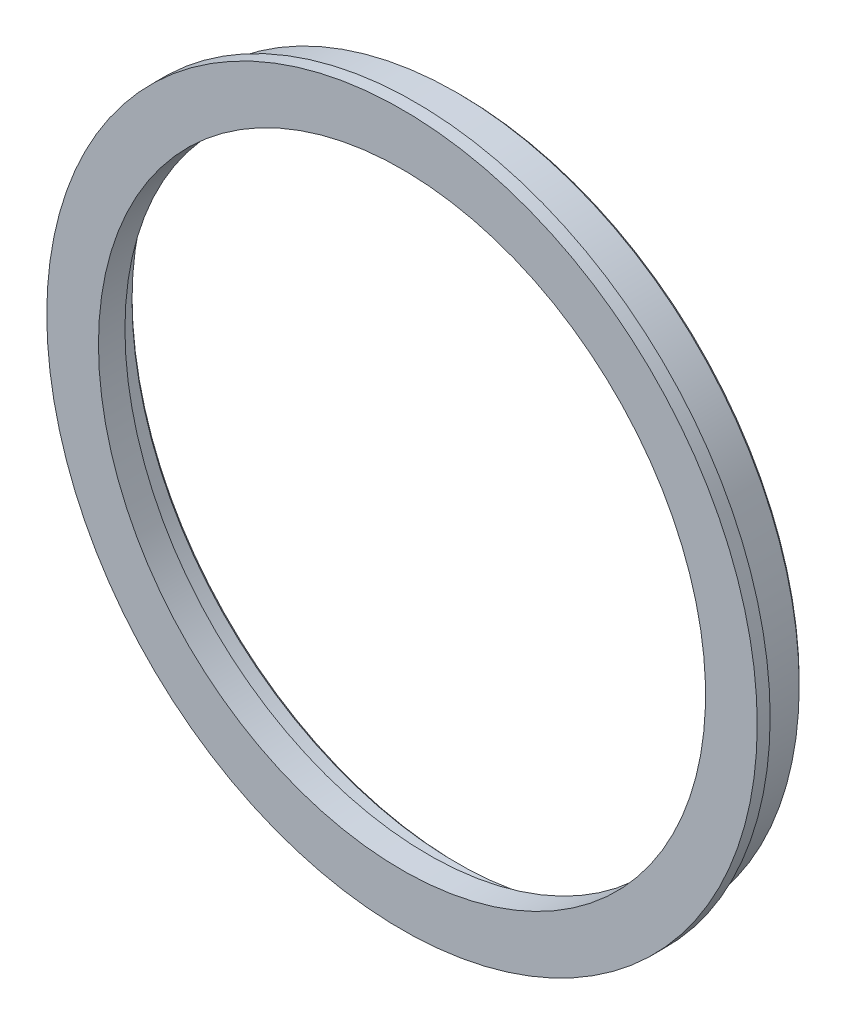
SolidWorks part; units mm, degrees
ref_plane "Front Plane" through (0, 0, 0) normal (0, 0, 1) x (1, 0, 0)
ref_plane "Top Plane" through (0, 0, 0) normal (0, 1, 0) x (1, 0, 0)
ref_plane "Right Plane" through (0, 0, 0) normal (1, 0, 0) x (0, 0, -1)
sketch "Sketch1" plane through (0, 0, 0) normal (0, 1, 0) x (1, 0, 0)
  line L0 (0, 69.1698) -> (0, -39.1508) construction
  line L1 (-62.5573, 0) -> (61.2977, 0) construction
  line L2 (50.3, 19) -> (50.3, 14.1)
  line L3 (50.3, 14.1) -> (47, 14.1)
  line L8 (49, 0) -> (49, 2.5)
  line L9 (49, 10) -> (55, 10)
  line L10 (55, 10) -> (55, 12)
  line L11 (55, 12) -> (53, 12)
  line L12 (53, 12) -> (53, 19)
  line L13 (53, 19) -> (50.3, 19)
  line L14 (49, 7.5) -> (48, 7.5)
  line L15 (48, 7.5) -> (48, 2.5)
  line L16 (48, 2.5) -> (49, 2.5)
  line L17 (49, 7.5) -> (49, 10)
  line L21 (47, 14.1) -> (47, 0)
  line L22 (47, 0) -> (49, 0)
  dimension "D1" = 55
  dimension "D3" = 53
  dimension "D4" = 2.7
  dimension "D5" = 4.9
  dimension "D6" = 7
  dimension "D7" = 2
  dimension "D8" = 49
  dimension "D9" = 2
  dimension "D10" = 10
  dimension "D12" = 1
  dimension "D13" = 5
  dimension "D14" = 2.5
revolve "Revolve1" add sketch "Sketch1" angle 360 about L0
chamfer "Chamfer1" distance 0.5 angle 45 8 edges at (-48, 0, -2.5) (-49, 0, -2.5) (-48, 0, -7.5) (-49, 0, -7.5) (-53, 0, -19) (-50.3, 0, -19) (-49, 0, -10) (-49, 0, 0)
sketch "Sketch2" plane through (0, 0, 0) normal (0, 1, 0) x (1, 0, 0)
  line L1 (-55, 10) -> (55.8978, 10)
  line L2 (-55, 10) -> (-55, -4.9943)
  line L3 (-55, -4.9943) -> (55.8978, -4.9943)
  line L4 (55.8978, 10) -> (55.8978, -4.9943)
extrude "Cut-Extrude1" cut sketch "Sketch2" against normal through all both and the other way through all
